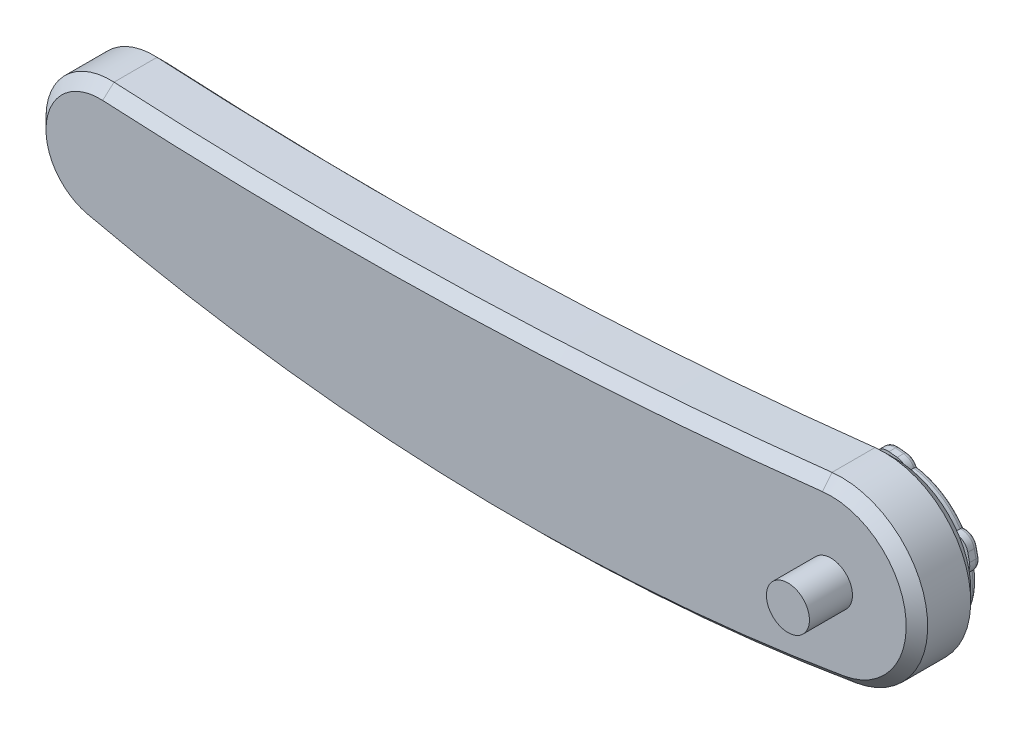
SolidWorks part; units mm, degrees
ref_plane "Front Plane" through (0, 0, 0) normal (0, 0, 1) x (1, 0, 0)
ref_plane "Top Plane" through (0, 0, 0) normal (0, 1, 0) x (1, 0, 0)
ref_plane "Right Plane" through (0, 0, 0) normal (1, 0, 0) x (0, 0, -1)
sketch "Sketch1" plane through (0, 0, 0) normal (0, 0, 1) x (1, 0, 0)
  line L0 (85, 0) -> (-85, 0) construction
  circle A0 centre (85, 0) radius 20
  circle A1 centre (-85, 0) radius 15
  arc A2 (-84.1861, 14.9779) -> (82.7465, 19.8726) centre (-29.9265, 1013.5048) ccw
  arc A3 (-88.3697, -14.6166) -> (88.3618, -19.7154) centre (12.7206, 423.8817) ccw
  point P4 (0, 0)
  dimension "D2" = 30
  dimension "D3" = 40
  dimension "D4" = 450
  dimension "D5" = 1000
  dimension "D1" = 170
extrude "Boss-Extrude2" add sketch "Sketch1" along normal mid plane 15 contours A1 | L0 A0 A2 A1 | A0 L0 A1 A3 | A0 region at (0.4487, -12.3679, 0) region at (1.0237, 7.6812, 0) region at (70.5043, 12.9448, 0) region at (-75.9246, -11.4057, 0)
chamfer "Chamfer1" distance 2.5 angle 45 8 edges at (-99.8523, 2.0996, 7.5) (-0.6174, 13.9344, 7.5) (104.8018, 2.8087, 7.5) (-0.2568, -25.9311, 7.5) (-0.2568, -25.9311, -7.5) (-99.8523, 2.0996, -7.5) (-0.6174, 13.9344, -7.5) (104.8018, 2.8087, -7.5)
sketch "Sketch3" plane through (0, 0, -7.5) normal (0, 0, -1) x (-1, 0, 0)
  circle A0 centre (-85, 0) radius 16.5
  dimension "D1" = 33
extrude "Boss-Extrude3" add sketch "Sketch3" along normal mid plane 5
sketch "Sketch4" plane through (0, 0, -10) normal (0, 0, -1) x (-1, 0, 0)
  line L0 (-85, 0) -> (-69.9921, -0.048)
  line L2 (-67.2448, 4.1787) -> (-68.028, 5.9265)
  line L3 (-72.2574, 7.3027) -> (-85, 0)
  line L4 (-85, 0) -> (-67.4523, 4.6417) construction
  line L5 (-85, 0) -> (-80.3166, 14.2585)
  line L6 (-88.0076, 14.3756) -> (-85, 0)
  line L7 (-83.4875, 18.1775) -> (-85.3918, 17.9727)
  line L8 (-85, 0) -> (-97.1134, 8.8603)
  line L9 (-99.6014, 1.5819) -> (-85, 0)
  line L10 (-101.8204, 7.0556) -> (-102.2142, 5.1812)
  line L11 (-85, 0) -> (-97.1698, -8.7825)
  line L12 (-91.0166, -13.3979) -> (-85, 0)
  line L13 (-96.9081, -13.8169) -> (-95.2471, -14.7705)
  line L14 (-85, 0) -> (-80.408, -14.2882)
  line L15 (-74.1171, -9.8623) -> (-85, 0)
  line L16 (-75.5392, -15.5949) -> (-74.1189, -14.3099)
  arc A0 (-68.028, 5.9265) -> (-72.2574, 7.3027) centre (-70.7657, 4.6998) ccw
  arc A1 (-67.2448, 4.1787) -> (-69.9921, -0.048) centre (-69.9825, 2.9519) cw
  arc A2 (-85.3918, 17.9727) -> (-88.0076, 14.3756) centre (-85.0711, 14.9899) ccw
  arc A3 (-83.4875, 18.1775) -> (-80.3166, 14.2585) centre (-83.1668, 15.1946) cw
  arc A4 (-102.2142, 5.1812) -> (-99.6014, 1.5819) centre (-99.2782, 4.5645) ccw
  arc A5 (-101.8204, 7.0556) -> (-97.1134, 8.8603) centre (-98.8845, 6.4389) cw
  arc A6 (-95.2471, -14.7705) -> (-91.0166, -13.3979) centre (-93.7533, -12.1689) ccw
  arc A7 (-96.9081, -13.8169) -> (-97.1698, -8.7825) centre (-95.4143, -11.2152) cw
  arc A8 (-74.1189, -14.3099) -> (-74.1171, -9.8623) centre (-76.1316, -12.0853) ccw
  arc A9 (-75.5392, -15.5949) -> (-80.408, -14.2882) centre (-77.5519, -13.3702) cw
  circle A10 centre (-85, 0) radius 2
  point P9 (-69.3828, 8.9501)
  point P36 (-85, 0)
  circle M13 centre (-85, 0) radius 16.5
  dimension "D3" = 3
  dimension "D4" = 3
  dimension "D6" = 4
  dimension "D1" = 30
  dimension "D2" = 18
  dimension "D5" = 5
extrude "Boss-Extrude5" add sketch "Sketch4" against normal up to surface (2.5 mm away) contours L4 A10 L0 A1 M13 | A10 L4 A0 L3 M13 | L4 A1 L2 M13 | L4 L2 A0 M13 | A10 L5 A3 A2 L6 M13 | A3 L7 A2 M13 | A10 L8 A5 A4 L9 M13 | A5 L10 A4 M13 | A10 L11 A7 A6 L12 M13 | A7 L13 A6 M13 | A10 L14 A9 A8 L15 M13 | A9 L16 A8 M13 region at (74.0061, 1.4226, -10) region at (74.7576, 4.1833, -10) region at (84.3813, 10.9644, -10) region at (95.2366, 3.9766, -10) region at (91.9453, -8.5068, -10) region at (79.0558, -9.2341, -10) region at (68.8747, 5.8512, -10) region at (67.9559, 2.7669, -10) region at (83.7877, 17.1, -10) region at (100.8884, 6.4371, -10) region at (96.0319, -13.1216, -10) region at (75.9296, -14.5467, -10) up to face at (101.5, 0, -7.5)
fillet "Fillet5" radius 1 20 edges at (93.7787, -15.1688, -10) (96.0776, -14.2937, -10) (98.2701, -12.1342, -10) (100.9775, -4.1193, -10) (102.1391, 3.6616, -10) (102.0173, 6.1184, -10) (100.6409, 8.8709, -10) (93.855, 13.9226, -10) (86.8139, 17.4318, -10) (84.4397, 18.0751, -10) (81.3966, 17.6167, -10) (74.4952, 12.7239, -10) (68.9819, 7.1118, -10) (67.6364, 5.0526, -10) (67.132, 2.0168, -10) (69.6527, -6.0588, -10) (73.2864, -13.0364, -10) (74.829, -14.9524, -10) (77.5604, -16.3702, -10) (86.0197, -16.4685, -10)
sketch "Sketch7" plane through (0, 0, -7.5) normal (0, 0, -1) x (-1, 0, 0)
  circle A0 centre (85, 0) radius 5
  dimension "D1" = 10
extrude "Cut-Extrude1" cut sketch "Sketch7" against normal blind 10
sketch "Sketch8" plane through (0, 0, 7.5) normal (0, 0, 1) x (1, 0, 0)
  circle A0 centre (85, 0) radius 5
  dimension "D1" = 10
extrude "Boss-Extrude6" add sketch "Sketch8" along normal blind 10
